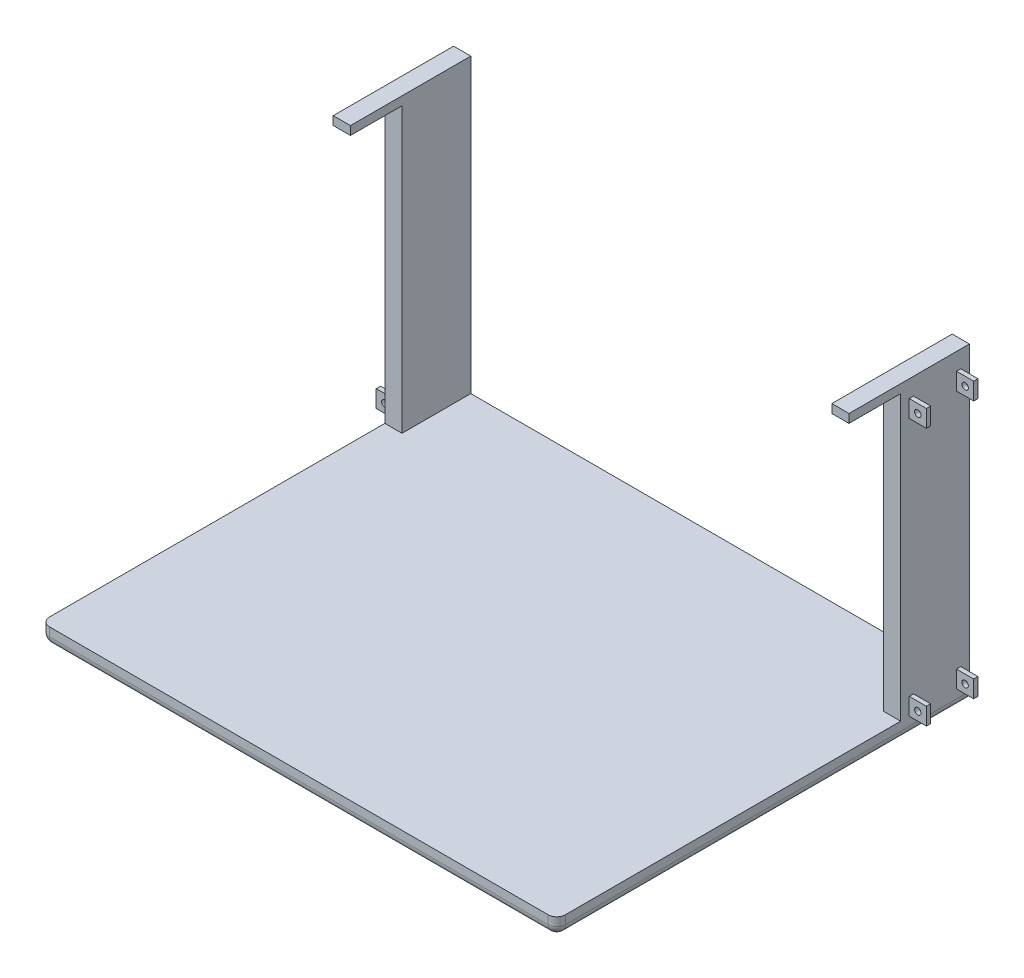
SolidWorks part; units mm, degrees
material "Cast Carbon Steel"
ref_plane "Front Plane" through (0, 0, 0) normal (0, 0, 1) x (1, 0, 0)
ref_plane "Top Plane" through (0, 0, 0) normal (0, 1, 0) x (1, 0, 0)
ref_plane "Right Plane" through (0, 0, 0) normal (1, 0, 0) x (0, 0, -1)
sketch "Sketch1" plane through (0, 0, 0) normal (0, 0, 1) x (1, 0, 0)
  line L0 (0, 0) -> (762, 0)
  line L1 (55, 0) -> (-55, 0) construction
  line L2 (762, 0) -> (762, 381)
  line L4 (762, 381) -> (0, 381)
  line L5 (762, 381) -> (762, 0)
  line L6 (762, 0) -> (0, 0)
  line L7 (0, 381) -> (0, 0)
  dimension "D1" = 762
  dimension "D2" = 381
extrude "Base Structure" add sketch "Sketch1" against normal blind 609.6 contours L4 L7 L0 L2 region at (381, 190.5, 0)
sketch "Sketch3" plane through (0, 0, -609.6) normal (0, 0, -1) x (-1, 0, 0)
  line L0 (335.28, 0) -> (-335.28, 0) construction
  line L1 (-736.6, 355.6) -> (-25.4, 355.6)
  line L2 (-736.6, 355.6) -> (-736.6, 25.4)
  line L3 (-736.6, 25.4) -> (-25.4, 25.4)
  line L4 (-25.4, 355.6) -> (-25.4, 25.4)
  line L5 (-762, 381) -> (0, 381) construction
  line L6 (-762, 0) -> (-762, 381) construction
  line L7 (0, 381) -> (0, 0) construction
  dimension "D1" = 25.4
  dimension "D2" = 25.4
  dimension "D3" = 25.4
  dimension "D4" = 25.4
extrude "Shell Cut" cut sketch "Sketch3" against normal blind 584.2
ref_plane "Mid Plane for Stability Holder" through (0, 0, -558.8) normal (0, 0, 1) x (1, 0, 0)
sketch "Sketch5" plane through (0, 0, -558.8) normal (0, 0, 1) x (1, 0, 0)
  line L0 (762, 0) -> (762, 381) construction
  line L1 (762, 355.6) -> (787.4, 355.6)
  line L2 (762, 355.6) -> (762, 330.2)
  line L3 (762, 330.2) -> (787.4, 330.2)
  line L4 (787.4, 355.6) -> (787.4, 330.2)
  line L5 (762, 381) -> (0, 381) construction
  circle A0 centre (774.7, 342.9) radius 4.7625
  dimension "D3" = 9.525
  dimension "D1" = 774.7
  dimension "D2" = 50.8
  dimension "D4" = 12.7
  dimension "D5" = 12.7
extrude "Stability Holder Cut for Top" add sketch "Sketch5" along normal mid plane 76.2
sketch "Sketch7" plane through (787.4, 0, 0) normal (1, 0, 0) x (0, 0, -1)
  line L0 (520.7, 355.6) -> (596.9, 355.6) construction
  line L1 (527.05, 355.6) -> (590.55, 355.6)
  line L2 (527.05, 355.6) -> (527.05, 330.2)
  line L3 (527.05, 330.2) -> (590.55, 330.2)
  line L4 (590.55, 355.6) -> (590.55, 330.2)
  line L5 (520.7, 330.2) -> (596.9, 330.2) construction
  line L6 (520.7, 330.2) -> (520.7, 355.6) construction
  line L7 (596.9, 330.2) -> (596.9, 355.6) construction
  dimension "D1" = 6.35
  dimension "D2" = 6.35
extrude "Insude Cut of Stability Holders" cut sketch "Sketch7" against normal blind 25.4
ref_plane "2Middle Plane For Chassis, Vertical" through (381, 0, 0) normal (1, 0, 0) x (0, 0, -1)
sketch "Sketch14" plane through (0, 0, -609.6) normal (0, 0, -1) x (-1, 0, 0)
  line L0 (-762, 381) -> (0, 381) construction
  line L1 (-25.4, 355.6) -> (-736.6, 355.6)
  line L2 (-25.4, 355.6) -> (-25.4, 381)
  line L3 (-25.4, 381) -> (-736.6, 381)
  line L4 (-736.6, 355.6) -> (-736.6, 381)
  line L5 (-736.6, 355.6) -> (-736.6, 25.4) construction
  dimension "D1" = 0
extrude "Top Shelling" cut sketch "Sketch14" against normal blind 406.4
sketch "Sketch16" plane through (0, 0, -609.6) normal (0, 0, -1) x (-1, 0, 0)
  line L0 (335.28, 0) -> (-335.28, 0) construction
  line L1 (-736.6, 25.4) -> (-25.4, 25.4)
  line L2 (-736.6, 25.4) -> (-736.6, 0)
  line L3 (-736.6, 0) -> (-25.4, 0)
  line L4 (-25.4, 25.4) -> (-25.4, 0)
  line L5 (-762, 0) -> (-762, 381) construction
  line L6 (-762, 0) -> (0, 0)
  line L7 (-762, 0) -> (-762, -76.2)
  line L8 (-762, -76.2) -> (0, -76.2)
  line L9 (0, 0) -> (0, -76.2)
  line L11 (-736.6, -50.8) -> (-25.4, -50.8)
  line L12 (-736.6, -50.8) -> (-736.6, 0)
  line L13 (-736.6, 0) -> (-25.4, 0)
  line L14 (-25.4, -50.8) -> (-25.4, 0)
  line M8 (-25.4, 25.4) -> (-736.6, 25.4)
  line M12 (-762, 0) -> (0, 0)
  dimension "D1" = 76.2
  dimension "D2" = 762
  dimension "D3" = 711.2
  dimension "D4" = 25.4
extrude "Bottom Extension" add sketch "Sketch16" against normal up to surface (609.6 mm away) contours L14 L11 L12 L7 L8 L9 M12 | L11 L14 L12 M12 region at (381, -59.0176, -609.6) region at (381, -25.4, -609.6) up to face at (381, 190.5, 0)
extrude "Bottom Shelling" cut sketch "Sketch16<6>" against normal blind 584.2 contours L4 L2 M8 M12 | L11 L14 L12 M12 region at (381, 12.7, -609.6) region at (381, -25.4, -609.6)
sketch "Sketch16<6>" plane through (0, 0, -609.6) normal (0, 0, -1) x (-1, 0, 0) same geometry as "Sketch16"
ref_plane "Plane4" through (0, 152.4, 0) normal (0, 1, 0) x (1, 0, 0)
mirror "Mirror5" about plane through (0, 152.4, 0) normal (0, 1, 0) of "Stability Holder Cut for Top"
sketch "Sketch17" plane through (787.4, 0, 0) normal (1, 0, 0) x (0, 0, -1)
  line L0 (520.7, -50.8) -> (596.9, -50.8) construction
  line L1 (520.7, -25.4) -> (527.05, -25.4)
  line L2 (520.7, -25.4) -> (520.7, -50.8)
  line L3 (520.7, -50.8) -> (527.05, -50.8)
  line L4 (527.05, -25.4) -> (527.05, -50.8)
  line L5 (520.7, -50.8) -> (596.9, -50.8) construction
  line L6 (596.9, -25.4) -> (590.55, -25.4)
  line L7 (596.9, -25.4) -> (596.9, -50.8)
  line L8 (596.9, -50.8) -> (590.55, -50.8)
  line L9 (590.55, -25.4) -> (590.55, -50.8)
  line L11 (527.05, -25.4) -> (590.55, -25.4)
  line L12 (527.05, -25.4) -> (527.05, -50.8)
  line L13 (527.05, -50.8) -> (590.55, -50.8)
  line L14 (590.55, -25.4) -> (590.55, -50.8)
  line M6 (596.9, -25.4) -> (520.7, -25.4)
  line M8 (520.7, -50.8) -> (596.9, -50.8)
  dimension "D1" = 6.35
  dimension "D2" = 6.35
extrude "Bottom Stabilty Holder Shell Cut" cut sketch "Sketch17" against normal up to surface (25.4 mm away) contours L9 L4 M6 M8 region at (787.4, -38.1, -558.8) up to face at (762, -38.1, -558.8)
sketch "Sketch18" plane through (762, 0, 0) normal (1, 0, 0) x (0, 0, -1)
  line L0 (0, 251.46) -> (0, -251.46) construction
  line L1 (0, -76.2) -> (609.6, -76.2) construction
  line L2 (0, -76.2) -> (0, 381) construction
  line L3 (609.6, -76.2) -> (609.6, 381) construction
  line L9 (609.6, 381) -> (0, 381) construction
  line L10 (508, -50.8) -> (0, -50.8)
  line L11 (508, -50.8) -> (508, 355.6)
  line L12 (508, 355.6) -> (0, 355.6)
  line L13 (0, -50.8) -> (0, 355.6)
  point P0 (0, 177.8)
  point P5 (0, -50.8)
  point P6 (508, -50.8)
  dimension "D1" = 254
  dimension "D2" = 25.4
  dimension "D3" = 101.6
  dimension "D4" = 25.4
  dimension "D5" = 25.4
  dimension "D6" = 0
extrude "3/4Shell Front Chassis Cut" cut sketch "Sketch18" against normal through all
ref_plane "Mid Plane For Chassis, Horizontal" through (0, 0, -12.7) normal (0, 0, 1) x (1, 0, 0)
sketch "Sketch19" plane through (0, 0, -12.7) normal (0, 0, 1) x (1, 0, 0)
  line L0 (749.3, -51.8465) -> (749.3, 25.2017)
  line L1 (673.1, 101.4017) -> (88.9, 101.4017)
  line L2 (12.7, 25.2017) -> (12.7, -51.8465)
  line L3 (762, -76.2) -> (762, -50.8) construction
  line L5 (0, -50.8) -> (0, -76.2) construction
  arc A0 (749.3, 25.2017) -> (673.1, 101.4017) centre (673.1, 25.2017) ccw
  arc A1 (12.7, 25.2017) -> (88.9, 101.4017) centre (88.9, 25.2017) cw
  dimension "D3" = 76.2
  dimension "D4" = 76.2
  dimension "D1" = 12.7
  dimension "D2" = 12.7
  dimension "D5" = 101.4017
  dimension "D6" = 51.8465
fillet "Fillet Corner of Front Chassis" radius 12.7 1 edges at (762, -63.5, 0)
ref_plane "Mid Plane of Wall" through (749.3, 0, 0) normal (1, 0, 0) x (0, 0, -1)
sketch "Sketch48" plane through (749.3, 0, 0) normal (1, 0, 0) x (0, 0, -1)
  line L0 (50.8, 25.4) -> (520.7, 203.2)
  line L4 (12.7, -50.8) -> (508, -50.8) construction
  line L6 (12.7, -50.8) -> (508, -50.8) construction
  dimension "D1" = 76.2
  dimension "D3" = 254
  dimension "D4" = 50.8
  dimension "D5" = 520.7
ref_plane "Mid Plane of Chassis, Vertical" through (508, 0, 0) normal (1, 0, 0) x (0, 0, -1)
sketch "Sketch68" plane through (508, 0, 0) normal (1, 0, 0) x (0, 0, -1)
  line L0 (15.24, 104.14) -> (317.5, 368.3)
  line L2 (203.2, 355.6) -> (203.2, 381) construction
  line L3 (508, 355.6) -> (0, 355.6) construction
  dimension "D1" = 15.24
  dimension "D2" = 114.3
  dimension "D3" = 12.7
  dimension "D4" = 104.14
sketch "Sketch87" plane through (508, 0, 0) normal (1, 0, 0) x (0, 0, -1)
  circle A0 centre (317.5, 368.3) radius 12.7
  dimension "D1" = 25.4
ref_plane "Plane for Steering Rack Holder" through (0, 368.3, 0) normal (0, 1, 0) x (1, 0, 0)
sketch "Sketch95" plane through (762, 0, 0) normal (1, 0, 0) x (0, 0, -1)
  line L0 (0, 251.46) -> (0, -251.46) construction
  line L1 (508, 355.6) -> (0, 355.6)
  line L2 (508, 355.6) -> (508, 381)
  line L3 (508, 381) -> (0, 381)
  line L4 (0, 355.6) -> (0, 381)
  line L5 (609.6, 381) -> (0, 381) construction
extrude "Cut Top Extrusion of Chassis" cut sketch "Sketch95" against normal through all
ref_plane "3Mid Plane of Chassis, Vertical" through (0, 0, -317.5) normal (0, 0, 1) x (1, 0, 0)
sketch "Sketch104" plane through (0, 0, -317.5) normal (0, 0, 1) x (1, 0, 0)
  line L0 (508, 368.3) -> (749.3, 368.3)
  line L1 (508, 355.6) -> (508, 381) construction
  line L2 (749.3, -251.46) -> (749.3, 251.46) construction
  line L3 (749.3, 368.3) -> (749.3, 127)
  line L4 (749.3, 25.4) -> (749.3, 203.2) construction
  line L5 (508, 368.3) -> (12.7, 368.3)
  line L6 (12.7, 368.3) -> (12.7, 127)
  dimension "D1" = 241.3
  dimension "D2" = 495.3
  dimension "D3" = 241.3
ref_plane "2Mid Plane Of wall, Vertical" through (749.3, 0, 0) normal (1, 0, 0) x (0, 0, -1)
sketch "Sketch118" plane through (749.3, 0, 0) normal (1, 0, 0) x (0, 0, -1)
  line L0 (317.5, 368.3) -> (508, 368.3)
  line L1 (508, -50.8) -> (508, 381) construction
  line L2 (13.97, 368.3) -> (-13.97, 368.3) construction
ref_plane "3Mid Plane Of wall, Vertical" through (762, 0, 0) normal (1, 0, 0) x (0, 0, -1)
sketch "Sketch171" plane through (762, 0, 0) normal (1, 0, 0) x (0, 0, -1)
  line L6 (508, 381) -> (431.7099, 381)
  line L7 (508, 381) -> (508, 368.3)
  line L8 (508, 368.3) -> (431.7099, 368.3)
  line L9 (431.7099, 381) -> (431.7099, 368.3)
  dimension "D1" = 12.7
  dimension "D2" = 76.2901
extrude "Extrusion of Steering Rack Holder" add sketch "Sketch171" against normal blind 25.4
sketch "Sketch172" plane through (0, 0, 0) normal (-1, 0, 0) x (0, 0, 1)
  line L1 (-508, 381) -> (-431.8, 381)
  line L2 (-508, 381) -> (-508, 368.3)
  line L3 (-508, 368.3) -> (-431.8, 368.3)
  line L4 (-431.8, 381) -> (-431.8, 368.3)
  dimension "D1" = 76.2
  dimension "D2" = 12.7
extrude "Extrusion of Other Steering Rack Holder" add sketch "Sketch172" against normal blind 25.4
mirror "Mirrors Stability Holders" about plane through (381, 0, 0) normal (1, 0, 0) of "Mirror5", "Stability Holder Cut for Top"
sketch "Sketch173" plane through (-25.4, 0, 0) normal (-1, 0, 0) x (0, 0, 1)
  line L0 (-520.7, 355.6) -> (-596.9, 355.6) construction
  line L1 (-590.55, 355.6) -> (-527.05, 355.6)
  line L2 (-590.55, 355.6) -> (-590.55, -50.8)
  line L3 (-590.55, -50.8) -> (-527.05, -50.8)
  line L4 (-527.05, 355.6) -> (-527.05, -50.8)
  line L5 (-520.7, -50.8) -> (-596.9, -50.8) construction
  line L6 (-596.9, 330.2) -> (-596.9, 355.6) construction
  line L7 (-520.7, -25.4) -> (-520.7, -50.8) construction
  dimension "D1" = 6.35
  dimension "D2" = 6.35
extrude "Extrusion of Other Stability Holders Top and Bottom" cut sketch "Sketch173" against normal up to surface (25.4 mm away) up to face at (0, 342.9, -558.8)
fillet "Fillet of Right Corner of Front Chassis" radius 12.7 1 edges at (0, -63.5, 0)
fillet "Fillet of Bottom Side of Front Chassis" radius 12.7 5 edges at (762, -76.2, -311.15) (758.2803, -76.2, -3.7197) (3.7197, -76.2, -3.7197) (381, -76.2, 0) (0, -76.2, -311.15)
ref_plane "Plane for Hollowing Diagonal/Middle Tube" through (508, 104.14, -15.24) normal (0, 0.6581, -0.753) x (-1, 0, 0)
sketch "Sketch205" plane through (508, 104.14, -15.24) normal (0, 0.6581, -0.753) x (-1, 0, 0)
  circle A0 centre (0, 0) radius 12.7
  circle A1 centre (0, 0) radius 8.7312
  circle A2 centre (99.3462, 0) radius 12.7
  circle A3 centre (99.3462, 0) radius 8.7313
  dimension "D1" = 25.4
  dimension "D2" = 17.4625
  dimension "D3" = 25.4
  dimension "D4" = 17.4625
  dimension "D5" = 408.6538
ref_plane "Mid Plane of Front Tubing, Vertical" through (0, 0, -12.7) normal (0, 0, 1) x (1, 0, 0)
ref_plane "4Mid Plane of Wall, Vertical" through (749.3, 0, 0) normal (1, 0, 0) x (0, 0, -1)
sketch "Sketch266" plane through (749.3, 0, 0) normal (1, 0, 0) x (0, 0, -1)
  line L0 (12.7, 25.4) -> (508, 25.4)
  line L1 (12.7, 101.4017) -> (12.7, 25.2017) construction
  line L2 (12.7, 25.2017) -> (12.7, -51.8465) construction
  line L3 (508, -50.8) -> (508, 368.3) construction
  dimension "D1" = 25.4
sketch "Sketch267" plane through (0, 0, -12.7) normal (0, 0, 1) x (1, 0, 0)
  circle A0 centre (749.3, 25.2017) radius 8.7312
  circle A1 centre (749.3, 25.2017) radius 12.7
  dimension "D1" = 17.4625
  dimension "D2" = 25.4
sketch "Sketch268" plane through (0, -50.8, 0) normal (0, 1, 0) x (1, 0, 0)
  line L0 (673.1, 12.7) -> (749.3, 12.7) construction
  line L1 (749.3, -244.475) -> (749.3, 244.475) construction
  circle A0 centre (749.3, 12.7) radius 12.7
  circle A1 centre (749.3, 12.7) radius 8.7312
  dimension "D1" = 25.4
  dimension "D2" = 17.4625
ref_plane "Horizontal Plane, Circle for Horizontal Tubing" through (0, 127, 0) normal (0, -1, 0) x (-1, 0, 0)
sketch "Sketch271" plane through (0, 127, 0) normal (0, -1, 0) x (-1, 0, 0)
  circle A0 centre (-749.3, 317.5) radius 8.7312
  circle A1 centre (-749.3, 317.5) radius 12.7
  dimension "D1" = 17.4625
  dimension "D2" = 25.4
ref_plane "Plane Relative to Circle for Diagonal Tubing, Conn. Front" through (749.3, 25.4, -50.8) normal (0, 0.3539, -0.9353) x (-1, 0, 0)
sketch "Sketch272" plane through (749.3, 25.4, -50.8) normal (0, 0.3539, -0.9353) x (-1, 0, 0)
  circle A0 centre (0, 0) radius 12.7
  circle A1 centre (0, 0) radius 8.7312
  dimension "D1" = 25.4
  dimension "D2" = 17.4625
ref_plane "Vertical Plane to Circle, Steering Rack" through (749.3, 368.3, -317.5) normal (0, 0, -1) x (-1, 0, 0)
sketch "Sketch273" plane through (0, 0, -508) normal (0, 0, 1) x (1, 0, 0)
  line L0 (0, -50.8) -> (0, 368.3) construction
  line L1 (12.7, -50.8) -> (749.3, -50.8) construction
  line L2 (25.4, 368.3) -> (0, 368.3) construction
  circle A0 centre (12.7, 25.4) radius 12.7
  circle A1 centre (12.7, 355.6) radius 12.7
  dimension "D2" = 25.4
  dimension "D5" = 25.4
  dimension "D1" = 12.7
  dimension "D3" = 76.2
  dimension "D4" = 12.7
ref_plane "Plane5" through (12.7, 0, 0) normal (-1, 0, 0) x (0, 0, 1)
sketch "Sketch274" plane through (12.7, 0, 0) normal (-1, 0, 0) x (0, 0, 1)
  line L0 (-520.7, 203.2) -> (-50.8, 25.4)
sketch "Sketch275" plane through (0, 0, -508) normal (0, 0, 1) x (1, 0, 0)
  line L0 (736.6, -50.8) -> (736.6, 368.3) construction
  line L1 (25.4, 368.3) -> (25.4, -50.8) construction
  line L2 (25.4, 368.3) -> (0, 368.3) construction
  circle A0 centre (749.3, 355.6) radius 12.7
  circle A1 centre (749.3, 355.6) radius 8.7312
  circle A2 centre (12.7, 355.6) radius 8.7313
  circle A3 centre (12.7, 355.6) radius 12.7
  dimension "D1" = 25.4
  dimension "D2" = 17.4625
  dimension "D7" = 17.4625
  dimension "D8" = 25.4
  dimension "D3" = 12.7
  dimension "D4" = 12.7
  dimension "D5" = 12.7
  dimension "D6" = 12.7
